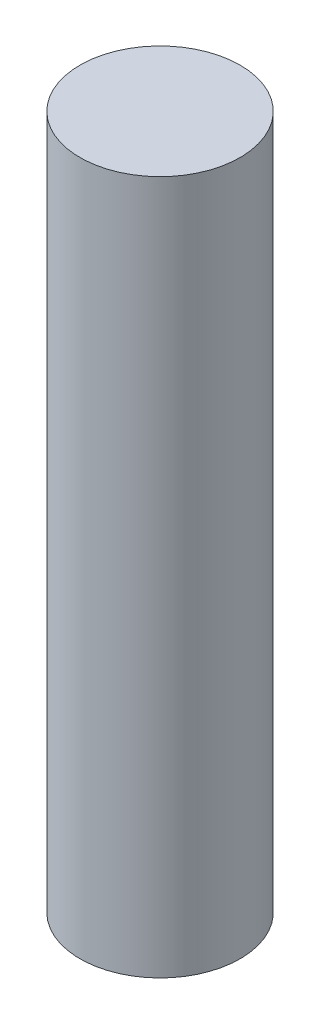
SolidWorks part; units mm, degrees
ref_plane "Front Plane" through (0, 0, 0) normal (0, 0, 1) x (1, 0, 0)
ref_plane "Top Plane" through (0, 0, 0) normal (0, 1, 0) x (1, 0, 0)
ref_plane "Right Plane" through (0, 0, 0) normal (1, 0, 0) x (0, 0, -1)
sketch "Sketch1" plane through (0, 0, 0) normal (0, 1, 0) x (1, 0, 0)
  circle A0 centre (0, 0) radius 3
  point P3 (0, 0)
  dimension "D1" = 6
extrude "Boss-Extrude1" add sketch "Sketch1" along normal blind 26
